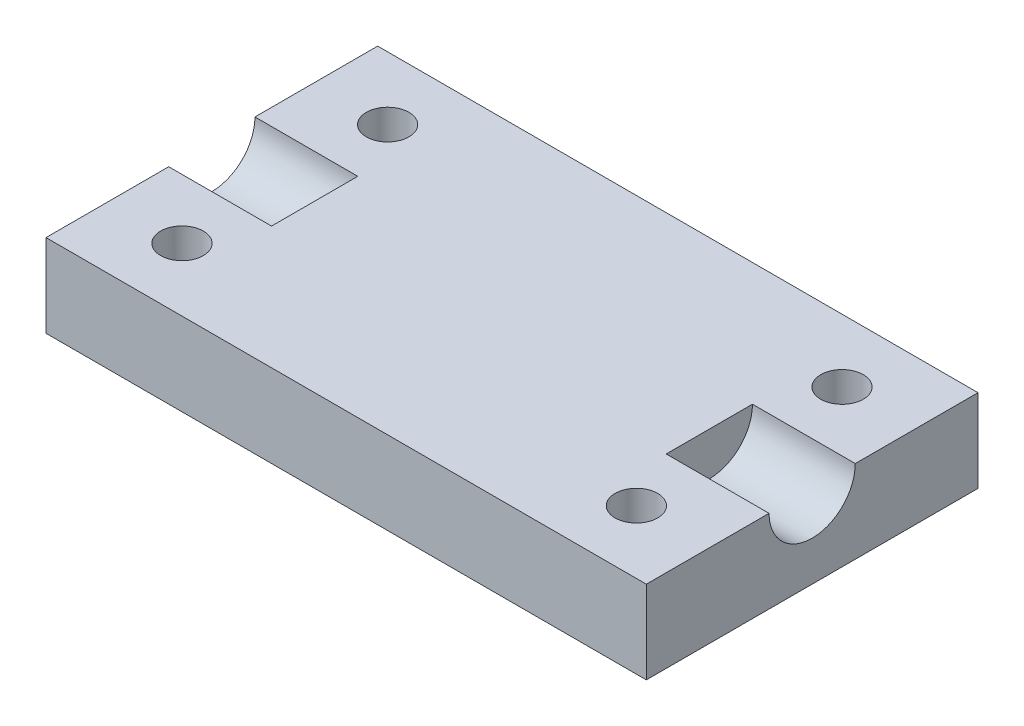
SolidWorks part; units mm, degrees
ref_plane "Front Plane" through (0, 0, 0) normal (0, 0, 1) x (1, 0, 0)
ref_plane "Top Plane" through (0, 0, 0) normal (0, 1, 0) x (1, 0, 0)
ref_plane "Right Plane" through (0, 0, 0) normal (1, 0, 0) x (0, 0, -1)
sketch "Sketch1" plane through (0, 0, 0) normal (0, 1, 0) x (1, 0, 0)
  line L1 (-22.987, -12.7) -> (22.987, -12.7)
  line L2 (-22.987, -12.7) -> (-22.987, 12.7)
  line L3 (-22.987, 12.7) -> (22.987, 12.7)
  line L4 (22.987, -12.7) -> (22.987, 12.7)
  line L5 (-22.987, -12.7) -> (22.987, 12.7) construction
  line L6 (-22.987, 12.7) -> (22.987, -12.7) construction
  point P0 (0, 0)
  dimension "D1" = 45.974
  dimension "D2" = 25.4
extrude "Boss-Extrude1" add sketch "Sketch1" against normal blind 6.35
sketch "Sketch2" plane through (22.987, 0, 0) normal (1, 0, 0) x (0, 0, -1)
  line L0 (-12.7, 0) -> (12.7, 0) construction
  circle A0 centre (0, 0) radius 3.302
  dimension "D1" = 6.604
extrude "Cut-Extrude1" cut sketch "Sketch2" against normal blind 7.874
sketch "Sketch3" plane through (-22.987, 0, 0) normal (-1, 0, 0) x (0, 0, 1)
  circle A0 centre (0, 0) radius 3.302
  dimension "D1" = 6.604
extrude "Cut-Extrude2" cut sketch "Sketch3" against normal blind 7.874
sketch "Sketch4" plane through (0, 0, 0) normal (0, 1, 0) x (1, 0, 0)
  line L0 (-22.987, -3.302) -> (-22.987, -12.7) construction
  line L1 (-22.987, 12.7) -> (-22.987, 3.302) construction
  line L2 (22.987, 3.302) -> (22.987, 12.7) construction
  line L3 (22.987, -12.7) -> (22.987, -3.302) construction
  line L4 (22.987, 12.7) -> (-22.987, 12.7) construction
  line L5 (-22.987, -12.7) -> (22.987, -12.7) construction
  circle A0 centre (17.399, -7.874) radius 1.632
  circle A1 centre (17.399, 7.874) radius 1.632
  circle A2 centre (-17.399, 7.874) radius 1.632
  circle A3 centre (-17.399, -7.874) radius 1.632
  dimension "D1" = 3.2639
  dimension "D2" = 3.2639
  dimension "D3" = 3.2639
  dimension "D4" = 3.2639
  dimension "D5" = 5.588
  dimension "D6" = 5.588
  dimension "D7" = 5.588
  dimension "D8" = 5.588
  dimension "D9" = 4.826
  dimension "D10" = 4.826
  dimension "D11" = 4.826
  dimension "D12" = 4.826
extrude "Cut-Extrude11" cut sketch "Sketch4" against normal up to next
